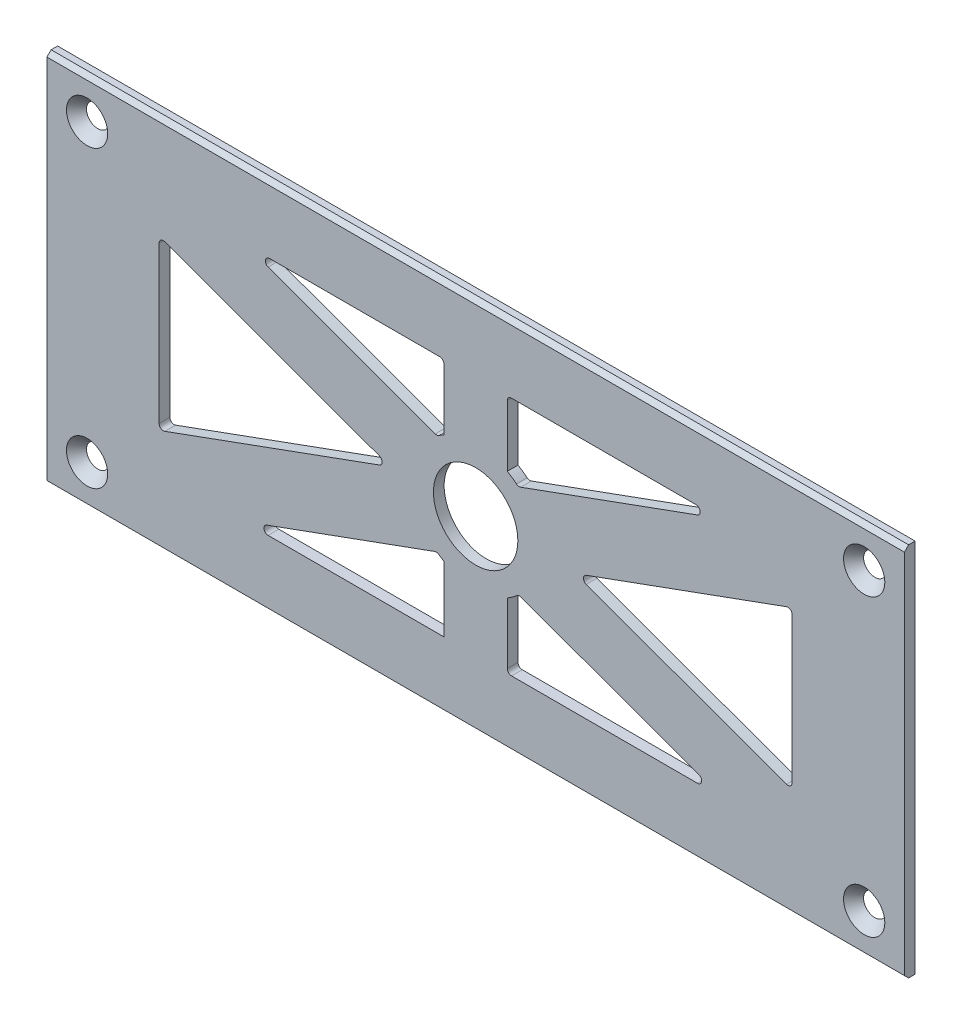
SolidWorks part; units mm, degrees
ref_plane "Front Plane" through (0, 0, 0) normal (0, 0, 1) x (1, 0, 0)
ref_plane "Top Plane" through (0, 0, 0) normal (0, 1, 0) x (1, 0, 0)
ref_plane "Right Plane" through (0, 0, 0) normal (1, 0, 0) x (0, 0, -1)
sketch "Sketch2" plane through (0, 0, 0) normal (0, 0, 1) x (1, 0, 0)
  line L1 (-101.6, -44.45) -> (101.6, -44.45)
  line L2 (-101.6, -44.45) -> (-101.6, 44.45)
  line L3 (-101.6, 44.45) -> (101.6, 44.45)
  line L4 (101.6, -44.45) -> (101.6, 44.45)
  line L5 (-101.6, -44.45) -> (101.6, 44.45) construction
  line L6 (-101.6, 44.45) -> (101.6, -44.45) construction
  circle A19 centre (0, 0) radius 10
  point P0 (0, 0)
  dimension "D6" = 20
  dimension "D2" = 88.9
  dimension "D4" = 203.2
extrude "Boss-Extrude1" add sketch "Sketch2" along normal mid plane 2.54
sketch "Sketch3" plane through (0, 0, 1.27) normal (0, 0, 1) x (1, 0, 0)
  line L0 (-101.6, 34.925) -> (-92.075, 34.925) construction
  line L1 (-101.6, 44.45) -> (-101.6, -44.45) construction
  line L2 (-92.075, 34.925) -> (-92.075, 44.45) construction
  line L3 (101.6, 44.45) -> (-101.6, 44.45) construction
  line L4 (92.075, 44.45) -> (92.075, 34.925) construction
  line L5 (92.075, 34.925) -> (101.6, 34.925) construction
  line L6 (101.6, -44.45) -> (101.6, 44.45) construction
  line L7 (92.075, -44.45) -> (92.075, -34.925) construction
  line L8 (-101.6, -44.45) -> (101.6, -44.45) construction
  line L9 (92.075, -34.925) -> (101.6, -34.925) construction
  line L10 (-92.075, -44.45) -> (-92.075, -34.925) construction
  line L11 (-92.075, -34.925) -> (-101.6, -34.925) construction
  circle A0 centre (-92.075, 34.925) radius 2.5527
  circle A1 centre (-92.075, -34.925) radius 2.5527
  circle A2 centre (92.075, -34.925) radius 2.5527
  circle A3 centre (92.075, 34.925) radius 2.5527
  dimension "D2" = 5.1054
  dimension "D1" = 9.525
extrude "Cut-Extrude1" cut sketch "Sketch3" against normal through all
hole_wizard "CSK for #10 Oval Head Machine Screw1" positions "Sketch5" profile "Sketch6" countersink size "#10" standard "ANSI Inch" end condition through all
sketch "Sketch5" plane through (0, 0, 1.27) normal (0, 0, 1) x (1, 0, 0)
  point P0 (-92.075, 34.925)
  point P3 (-92.075, -34.925)
  point P6 (92.075, -34.925)
  point P9 (92.075, 34.925)
sketch "Sketch6" plane through (-92.075, 34.925, 1.27) normal (1, 0, 0) x (0, -1, 0)
  line L0 (0, 0) -> (0, 2.54)
  line L1 (0, 2.54) -> (2.5527, 2.54)
  line L2 (2.5527, 2.54) -> (2.5527, 2.6882)
  line L3 (2.5527, 2.6882) -> (4.8895, 0)
  line L5 (4.8895, 0) -> (0, 0)
  line L6 (-2.5527, 2.6882) -> (-4.8895, 0) construction
  line L11 (0, -6.35) -> (0, 107.95) construction
  dimension "Thru Hole Dia." = 5.1054
  dimension "Thru Hole Depth" = 2.54
  dimension "Near C'Sink Dia." = 9.779
  dimension "Near C'Sink Angle" = 82
sketch "Sketch7" plane through (0, 0, 1.27) normal (0, 0, 1) x (1, 0, 0)
sketch "Sketch8" plane through (0, 0, 1.27) normal (0, 0, 1) x (1, 0, 0)
  line L0 (-7.5, 12.9904) -> (-7.5, 28.5)
  line L1 (-75, -28.5) -> (75, -28.5)
  line L2 (-75, -28.5) -> (-75, 28.5)
  line L3 (-75, 28.5) -> (75, 28.5)
  line L4 (75, -28.5) -> (75, 28.5)
  line L5 (-75, -28.5) -> (75, 28.5) construction
  line L6 (-75, 28.5) -> (75, -28.5) construction
  line L7 (7.5, 12.9904) -> (7.5, 28.5)
  line L8 (-9.057, 11.9571) -> (-54.5083, 28.5)
  line L9 (-75, 19.9957) -> (-14.881, -1.8858)
  line L10 (10.1873, -11.0099) -> (58.2408, -28.5)
  line L11 (14.6239, 3.3379) -> (75, -18.6372)
  line L12 (-9.1677, -11.8723) -> (-54.8518, -28.5)
  line L13 (-14.8638, 2.0171) -> (-75, -19.8707)
  line L14 (-7.5, -12.9904) -> (-7.5, -28.5)
  line L15 (7.5, -12.9904) -> (7.5, -28.5)
  line L16 (14.6543, -3.2018) -> (75, 18.7622)
  line L17 (10.0897, 11.0995) -> (57.8973, 28.5)
  line L18 (-7.5, -20.7452) -> (7.5, -20.7452)
  line L19 (0, -20.7452) -> (0, -15) construction
  line L20 (-44.9405, 9.0549) -> (-39.8102, 23.1503) construction
  line L21 (-32.0098, -20.1862) -> (-37.1401, -6.0908) construction
  circle A0 centre (0, 0) radius 15
  point P0 (0, 0)
  point P38 (-42.3753, 16.1026)
  point P41 (-34.5749, -13.1385)
  dimension "D1" = 30
  dimension "D2" = 150
  dimension "D3" = 57
  dimension "D4" = 20
  dimension "D5" = 20
  dimension "D6" = 15
  dimension "D7" = 15
extrude "Cut-Extrude2" cut sketch "Sketch8" against normal blind 10 contours A0 L12 L1 L14 | A0 L15 L1 L10 | L16 L11 L4 | A0 L17 L3 L7 | A0 L0 L3 L8 | L13 L9 L2 region at (-23.2179, 22.8309, 1.27) region at (24.4329, 22.4776, 1.27) region at (-56.7447, 0.0625, 1.27) region at (57.8743, 0.0625, 1.27) region at (-23.3395, -22.7942, 1.27) region at (24.5577, -22.4427, 1.27)
fillet "Fillet1" radius 1 17 edges at (-54.8518, -28.5, 0) (7.5, -28.5, 0) (-9.1677, -11.8723, 0) (10.1873, -11.0099, 0) (58.2408, -28.5, 0) (75, -18.6372, 0) (75, 18.7622, 0) (23.623, 0.0625, 0) (57.8973, 28.5, 0) (7.5, 28.5, 0) (10.0897, 11.0995, 0) (-54.5083, 28.5, 0) (-7.5, 28.5, 0) (-9.057, 11.9571, 0) (-20.234, 0.0625, 0) (-75, -19.8707, 0) (-75, 19.9957, 0)
chamfer "Chamfer1" distance 1 angle 45 2 edges at (0, -44.45, 1.27) (0, 44.45, 1.27)
